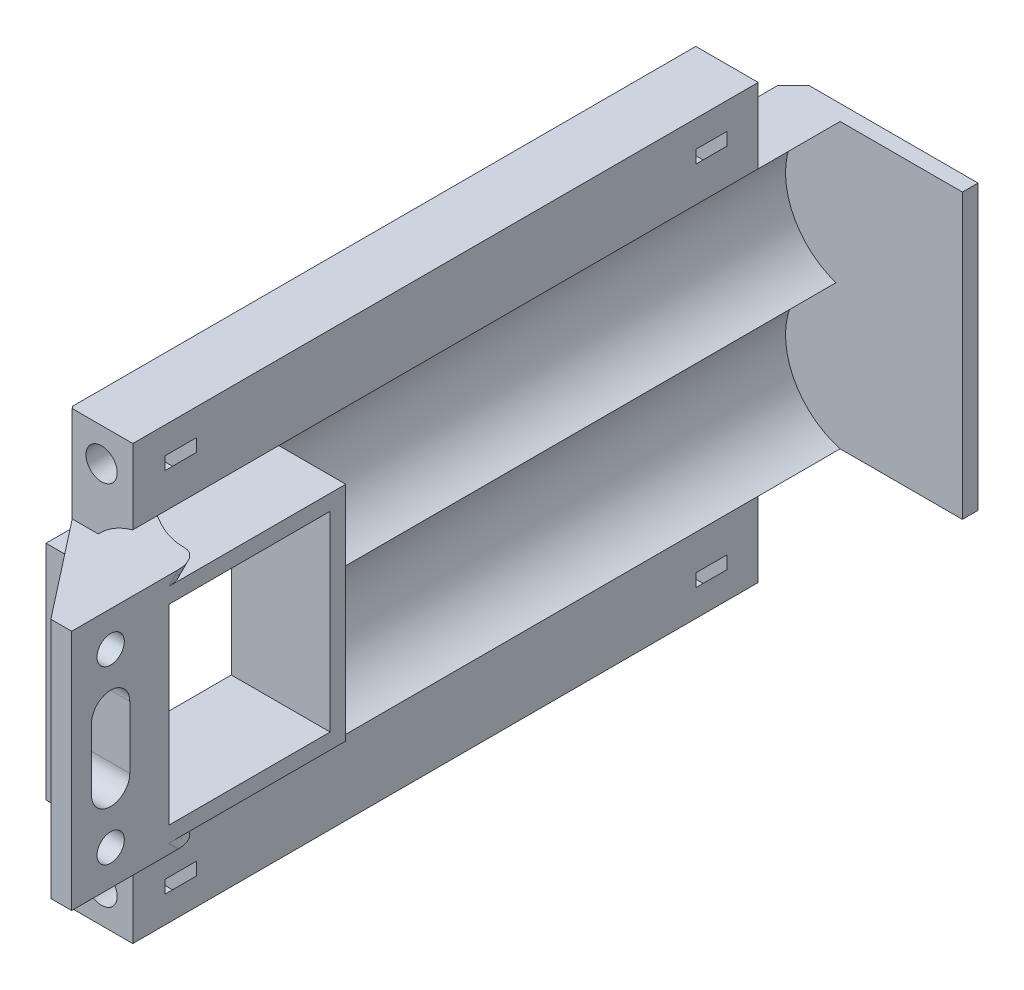
SolidWorks part; units mm, degrees
ref_plane "Front Plane" through (0, 0, 0) normal (0, 0, 1) x (1, 0, 0)
ref_plane "Top Plane" through (0, 0, 0) normal (0, 1, 0) x (1, 0, 0)
ref_plane "Right Plane" through (0, 0, 0) normal (1, 0, 0) x (0, 0, -1)
sketch "Sketch1" plane through (0, 0, 0) normal (0, 0, 1) x (1, 0, 0)
  line L1 (-39.9, 0.5) -> (-39.9, 19.5) construction
  line L2 (-40.4, 20.3348) -> (-40.4, 10.75)
  line L3 (-46.9, 10.75) -> (-39.9, 10.75) construction
  line L4 (-40.4, 10.75) -> (-48.3958, 10.75)
  line L5 (-48.3958, 10.75) -> (-48.3958, 66.25)
  line L6 (-48.3958, 66.25) -> (-40.4, 66.25)
  line L7 (-40.4, 66.25) -> (-40.4, 56.6652)
  circle A0 centre (-44.4, 15) radius 2 construction
  circle A1 centre (-44.4, 62) radius 2 construction
  circle A2 centre (-37.9, 47.5) radius 9.5
  circle A3 centre (-37.9, 47.5) radius 9.5 construction
  arc A4 (-40.4, 20.3348) -> (-40.9414, 38.5) centre (-37.9, 29.5) cw
  circle A5 centre (-37.9, 29.5) radius 9.5
  circle A6 centre (-37.9, 29.5) radius 9.5 construction
  arc A7 (-40.9414, 38.5) -> (-40.4, 56.6652) centre (-37.9, 47.5) cw
  circle A8 centre (-44.4, 15) radius 2
  circle A9 centre (-44.4, 62) radius 2
  point P23 (-47.3958, 29.217)
  dimension "D3" = 0.5
  dimension "D4" = 1
  dimension "D1" = 0.5
  dimension "D2" = 0.5
extrude "Boss-Extrude1" add sketch "Sketch1" along normal up to surface (80.1468 mm away)
sketch "Sketch2" plane through (-35.7348, 0, 0) normal (-1, 0, 0) x (0, 0, 1)
  line L0 (82.6468, 23) -> (80.1468, 23)
  line L1 (80.1468, 66.25) -> (80.1468, 10.75) construction
  line L2 (80.1468, 23) -> (80.1468, 54)
  line L3 (80.1468, 54) -> (82.6468, 54)
  line L4 (92.6468, 54) -> (82.6468, 54)
  line L5 (82.6468, 54) -> (82.6468, 23)
  line L6 (82.6468, 23) -> (92.6468, 23)
  line L7 (92.6468, 23) -> (92.6468, 54)
  line L8 (92.6468, 54) -> (82.6468, 54)
  line L9 (82.6468, 54) -> (82.6468, 23) construction
  line L10 (82.6468, 23) -> (92.6468, 23)
  line L11 (92.6468, 23) -> (92.6468, 54)
  line L12 (87.6468, 34.5) -> (87.6468, 42.5) construction
  line L14 (85.1968, 34.5) -> (85.1968, 42.5)
  line L15 (90.0968, 34.5) -> (90.0968, 42.5)
  line L17 (87.6468, 27.5) -> (87.6468, 49.5) construction
  arc A1 (85.1968, 34.5) -> (90.0968, 34.5) centre (87.6468, 34.5) ccw
  circle A2 centre (87.6468, 38.5) radius 2.45
  circle A3 centre (87.6468, 38.5) radius 2.45 construction
  arc A4 (90.0968, 42.5) -> (85.1968, 42.5) centre (87.6468, 42.5) ccw
  circle A5 centre (87.6468, 27.5) radius 1.75
  circle A6 centre (87.6468, 49.5) radius 1.75
  point P15 (87.6468, 38.5)
  point P26 (87.6468, 38.5)
  dimension "D5" = 3.5
  dimension "D3" = 8
  dimension "D4" = 22
  dimension "D1" = 1
  dimension "D2" = 0
extrude "Boss-Extrude2" add sketch "Sketch2" along normal up to surface (12.661 mm away) up to face at (-48.3958, 38.5, 40.0734)
chamfer "Chamfer1" distance 10 angle 52 1 edges at (-48.3958, 38.5, 92.6468) first distance on face at (-42.0653, 38.5, 92.6468)
sketch "Sketch3" plane through (-48.3958, 0, 0) normal (-1, 0, 0) x (0, 0, 1)
  circle A0 centre (87.6468, 27.5) radius 3
  circle A1 centre (87.6468, 49.5) radius 3
  dimension "D1" = 6
extrude "Cut-Extrude1" cut sketch "Sketch3" against normal offset from surface (8.661 mm away) 4 up to face at (-35.7348, 49.5, 89.3968)
sketch "Sketch4" plane through (0, 0, 0) normal (0, 0, -1) x (-1, 0, 0)
  line L0 (40.4, 20.3348) -> (48.3958, 20.3348)
  line L1 (48.3958, 66.25) -> (48.3958, 10.75) construction
  line L2 (48.3958, 20.3348) -> (48.3958, 56.6652)
  line L3 (48.3958, 56.6652) -> (40.4, 56.6652)
  arc A0 (40.9414, 38.5) -> (40.4, 56.6652) centre (37.9, 47.5) ccw construction
  arc A1 (40.4, 20.3348) -> (40.9414, 38.5) centre (37.9, 29.5) ccw construction
  arc A2 (40.9414, 38.5) -> (40.4, 56.6652) centre (37.9, 47.5) ccw
  arc A3 (40.4, 20.3348) -> (40.9414, 38.5) centre (37.9, 29.5) ccw
extrude "Boss-Extrude3" add sketch "Sketch4" along normal offset from surface (10.5 mm away) 2
sketch "Sketch5" plane through (0, 0, -10.5) normal (0, 0, -1) x (-1, 0, 0)
  line L0 (40.4, 56.6652) -> (48.3958, 56.6652) construction
  line L1 (48.3958, 20.3348) -> (24.7348, 20.3348)
  line L2 (48.3958, 20.3348) -> (48.3958, 56.6652)
  line L3 (48.3958, 56.6652) -> (24.7348, 56.6652)
  line L4 (24.7348, 20.3348) -> (24.7348, 56.6652)
  line L6 (35.7348, 23) -> (35.7348, 54) construction
  dimension "D1" = 11
extrude "Boss-Extrude4" add sketch "Sketch5" along normal blind 2
sketch "Sketch6" plane through (0, 0, 0) normal (0, 0, -1) x (-1, 0, 0)
  line L0 (46.6372, 65.875) -> (48.3958, 65.875)
  line L1 (48.8745, 15) -> (46.6372, 18.875) construction
  line L2 (46.6372, 18.875) -> (42.1628, 18.875)
  line L3 (42.1628, 18.875) -> (39.9255, 15)
  line L4 (39.9255, 15) -> (42.1628, 11.125)
  line L5 (42.1628, 11.125) -> (46.6372, 11.125)
  line L6 (46.6372, 11.125) -> (48.8745, 15) construction
  line L7 (48.8745, 62) -> (46.6372, 65.875) construction
  line L8 (46.6372, 65.875) -> (42.1628, 65.875)
  line L9 (42.1628, 65.875) -> (39.9255, 62)
  line L10 (39.9255, 62) -> (42.1628, 58.125)
  line L11 (42.1628, 58.125) -> (46.6372, 58.125)
  line L12 (46.6372, 58.125) -> (48.8745, 62) construction
  line L13 (48.3958, 66.25) -> (48.3958, 56.6652) construction
  line L15 (48.3958, 65.875) -> (48.3958, 58.125)
  line L16 (48.3958, 58.125) -> (46.6372, 58.125)
  line L17 (46.6372, 18.875) -> (48.3958, 18.875)
  line L18 (48.3958, 20.3348) -> (48.3958, 10.75) construction
  line L19 (48.3958, 18.875) -> (48.3958, 11.125)
  line L20 (48.3958, 11.125) -> (46.6372, 11.125)
  circle A0 centre (44.4, 15) radius 3.875 construction
  circle A1 centre (44.4, 62) radius 3.875 construction
  dimension "D1" = 7.75
extrude "Cut-Extrude2" cut sketch "Sketch6" against normal blind 4 from offset 4 offset against normal yes
extrude "Cut-Extrude3" cut sketch "Sketch6<2>" against normal blind 4 from offset 72 offset against normal yes
sketch "Sketch6<2>" plane through (0, 0, 0) normal (0, 0, -1) x (-1, 0, 0) same geometry as "Sketch6"
chamfer "Chamfer2" distance 2 angle 45 1 edges at (-48.3958, 38.5, -12.5)
sketch "Sketch7" plane through (-48.3958, 0, 0) normal (-1, 0, 0) x (0, 0, 1)
  line L0 (79.8473, 10.75) -> (79.8473, 66.25) construction
  line L1 (60.6468, 27.25) -> (80.1468, 27.25)
  line L2 (60.6468, 27.25) -> (60.6468, 49.75)
  line L3 (60.6468, 49.75) -> (80.1468, 49.75)
  line L4 (80.1468, 27.25) -> (80.1468, 49.75)
  line L5 (60.6468, 27.25) -> (80.1468, 49.75) construction
  line L6 (60.6468, 49.75) -> (80.1468, 27.25) construction
  line L7 (80.1468, 54) -> (80.1468, 23) construction
  point P0 (70.3968, 38.5)
  point P7 (79.8473, 38.5)
  dimension "D1" = 19.5
  dimension "D2" = 22.5
extrude "Cut-Extrude4" cut sketch "Sketch7" against normal through all
chamfer "Chamfer3" distance 7 angle 45 2 edges at (-46.2538, 52.0238, 80.1468) (-46.2538, 24.9762, 80.1468)
fillet "Fillet2" radius 2 2 edges at (-35.7348, 50.9474, 78.5758)
sketch "Sketch9" plane through (-48.3958, 0, 0) normal (-1, 0, 0) x (0, 0, 1)
  line L1 (59.5218, 26.25) -> (81.2718, 26.25)
  line L2 (59.5218, 26.25) -> (59.5218, 50.75)
  line L3 (59.5218, 50.75) -> (81.2718, 50.75)
  line L4 (81.2718, 26.25) -> (81.2718, 50.75)
  line L5 (59.5218, 26.25) -> (81.2718, 50.75) construction
  line L6 (59.5218, 50.75) -> (81.2718, 26.25) construction
  point P0 (70.3968, 38.5)
  dimension "D1" = 24.5
  dimension "D2" = 21.75
extrude "Cut-Extrude5" cut sketch "Sketch9" against normal blind 2
sketch "Sketch10" plane through (-48.3958, 0, 0) normal (-1, 0, 0) x (0, 0, 1)
  line L4 (79.8473, 26.25) -> (81.2718, 26.25) construction
  line L5 (81.2718, 50.75) -> (79.8473, 50.75) construction
  line L6 (81.2718, 26.25) -> (81.2718, 50.75) construction
  line L7 (79.8473, 50.75) -> (59.5218, 50.75) construction
  line L8 (57.5218, 52.75) -> (57.5218, 24.25)
  line L9 (57.5218, 24.25) -> (83.2718, 24.25)
  line L10 (83.2718, 24.25) -> (83.2718, 52.75)
  line L11 (83.2718, 52.75) -> (57.5218, 52.75)
  line L12 (57.5218, 52.75) -> (57.5218, 24.25)
  line L13 (57.5218, 24.25) -> (83.2718, 24.25)
  line L14 (83.2718, 24.25) -> (83.2718, 52.75)
  line L15 (83.2718, 52.75) -> (57.5218, 52.75)
  line L16 (59.5218, 26.25) -> (79.8473, 26.25) construction
  line L17 (59.5218, 50.75) -> (59.5218, 26.25) construction
  line L18 (79.8473, 26.25) -> (81.2718, 26.25)
  line L19 (81.2718, 50.75) -> (79.8473, 50.75)
  line L20 (81.2718, 26.25) -> (81.2718, 50.75)
  line L21 (79.8473, 50.75) -> (59.5218, 50.75)
  line L22 (59.5218, 26.25) -> (79.8473, 26.25)
  line L23 (59.5218, 50.75) -> (59.5218, 26.25)
  dimension "D1" = 2
extrude "Boss-Extrude5" add sketch "Sketch10" against normal up to surface (12.661 mm away) up to face at (-35.7348, 49.5, 89.3968)
sketch "Sketch11" plane through (-35.7348, 0, 0) normal (1, 0, 0) x (0, 0, -1)
  line L0 (-59.5218, 26.25) -> (-59.5218, 50.75) construction
  line L1 (-59.5218, 50.75) -> (-80.1468, 50.75)
  line L2 (-59.5218, 50.75) -> (-59.5218, 26.25)
  line L3 (-59.5218, 26.25) -> (-80.1468, 26.25)
  line L4 (-80.1468, 50.75) -> (-80.1468, 26.25)
  line L5 (-59.5218, 50.75) -> (-80.1468, 26.25) construction
  line L6 (-59.5218, 26.25) -> (-80.1468, 50.75) construction
  line L7 (-80.1468, 26.25) -> (-59.5218, 26.25) construction
  point P0 (-69.8343, 38.5)
extrude "Cut-Extrude6" cut sketch "Sketch11" against normal through all both and the other way through all
